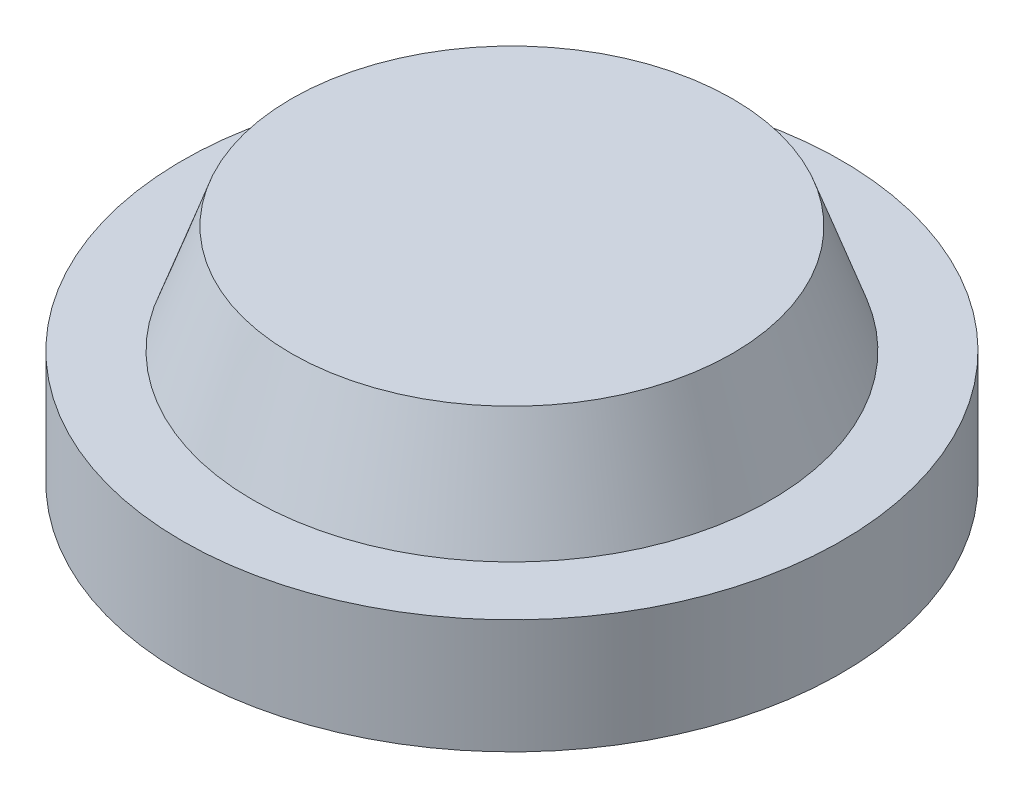
SolidWorks part; units mm, degrees
ref_plane "Front Plane" through (0, 0, 0) normal (0, 0, 1) x (1, 0, 0)
ref_plane "Top Plane" through (0, 0, 0) normal (0, 1, 0) x (1, 0, 0)
ref_plane "Right Plane" through (0, 0, 0) normal (1, 0, 0) x (0, 0, -1)
sketch "Sketch2" plane through (0, 0, 0) normal (0, 0, 1) x (1, 0, 0)
  line L0 (0, 0) -> (30.25, 0)
  line L1 (30.25, 0) -> (30.25, 10.5)
  line L2 (30.25, 10.5) -> (23.75, 10.5)
  line L3 (23.75, 10.5) -> (20.25, 20.4049)
  line L4 (20.25, 20.4049) -> (0, 20.4049)
  line L5 (0, 20.4049) -> (0, 0)
  dimension "D1" = 30.25
  dimension "D2" = 10.5
  dimension "D3" = 20.25
  dimension "D4" = 6.5
ref_axis "Axis1" through (0, 0, 0) along (0, 1, 0)
revolve "Revolve1" add sketch "Sketch2" angle 360 about L5
